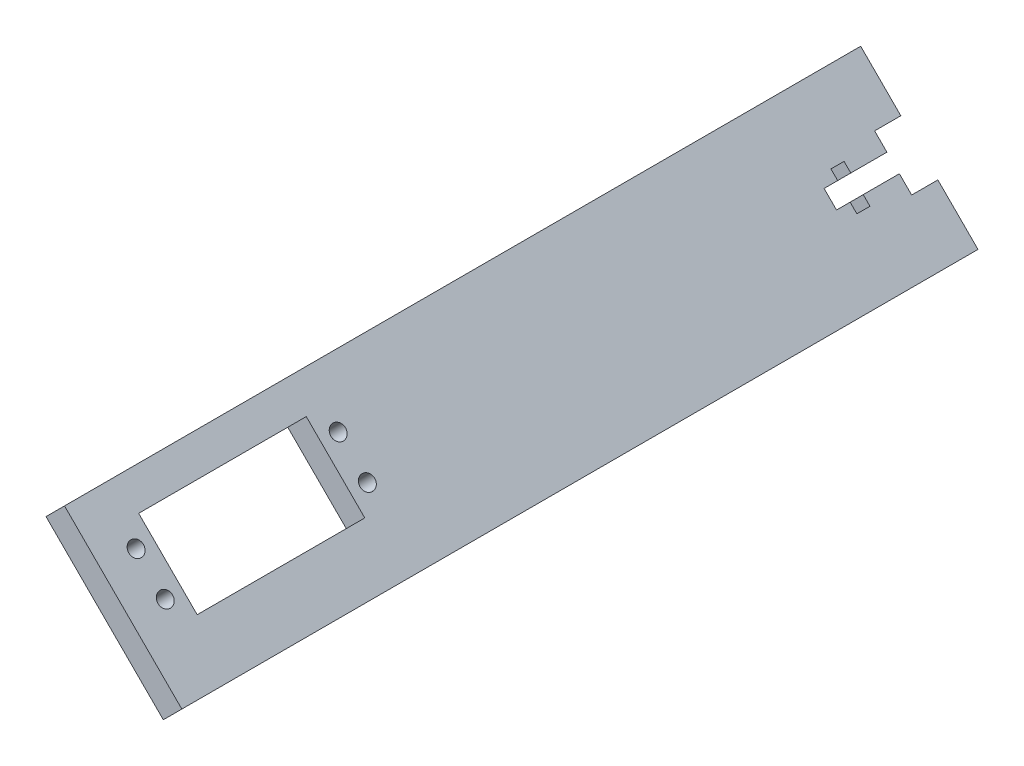
SolidWorks part; units mm, degrees
ref_plane "Front Plane" through (0, 0, 0) normal (0, 0, 1) x (1, 0, 0)
ref_plane "Top Plane" through (0, 0, 0) normal (0, 1, 0) x (1, 0, 0)
ref_plane "Right Plane" through (0, 0, 0) normal (1, 0, 0) x (0, 0, -1)
sketch "Sketch2" plane through (0, 0, 0) normal (0, 0, 1) x (1, 0, 0)
  line L0 (-71.1005, -144.0441) -> (-75.5906, -148.5343)
  line L1 (-71.1005, -144.0441) -> (-42.6562, -172.4884)
  line L2 (-75.5906, -148.5343) -> (-47.1463, -176.9785)
  line L3 (-42.6562, -172.4884) -> (-47.1463, -176.9785)
  line L4 (-75.5906, -148.5343) -> (-65.8586, -158.2663) construction
  line L5 (-61.3685, -153.7761) -> (-71.1005, -144.0441) construction
  line L6 (-47.1463, -176.9785) -> (-42.6562, -172.4884) construction
  line L7 (-71.1005, -144.0441) -> (-75.5906, -148.5343) construction
extrude "Boss-Extrude1" add sketch "Sketch2" along normal blind 186.69
sketch "Sketch3" plane through (-112.0624, -112.0624, 0) normal (-0.7071, -0.7071, 0) x (0, 0, 1)
  line L0 (0, -71.6921) -> (24.1393, -71.6921) construction
  line L1 (0, -51.579) -> (0, -91.8052) construction
  line B0 (0, -69.5585) -> (0, -73.8257)
  line B1 (11.938, -73.8257) -> (11.938, -76.1371)
  line B2 (11.938, -76.1371) -> (8.763, -76.1371)
  line B3 (8.763, -76.1371) -> (8.763, -73.8257)
  line B4 (8.763, -73.8257) -> (0, -73.8257)
  line B5 (11.938, -73.8257) -> (15.24, -73.8257)
  line B6 (15.24, -73.8257) -> (15.24, -69.5585)
  line B7 (11.938, -69.5585) -> (15.24, -69.5585)
  line B8 (8.763, -69.5585) -> (0, -69.5585)
  line B9 (8.763, -67.2471) -> (8.763, -69.5585)
  line B10 (11.938, -67.2471) -> (8.763, -67.2471)
  line B11 (11.938, -69.5585) -> (11.938, -67.2471)
sketch_block_instance "TSlot-1"
sketch_block "TSlot" parameters "D1"=3.302, "D2"=3.175
extrude "Cut-Extrude1" cut sketch "Sketch3" against normal through all
sketch "Sketch4" plane through (0, 0, 0) normal (0, 0, -1) x (-1, 0, 0)
  line L0 (75.5906, -148.5343) -> (65.8586, -158.2663) construction
  line L1 (65.8586, -158.2663) -> (61.3685, -153.7761) construction
  line L2 (61.3685, -153.7761) -> (71.1005, -144.0441) construction
  line L3 (71.1005, -144.0441) -> (75.5906, -148.5343) construction
  line L4 (42.6562, -172.4884) -> (52.3882, -162.7564) construction
  line L5 (52.3882, -162.7564) -> (56.8783, -167.2465) construction
  line L6 (56.8783, -167.2465) -> (47.1463, -176.9785) construction
  line L7 (47.1463, -176.9785) -> (42.6562, -172.4884) construction
  line L8 (75.5906, -148.5343) -> (65.8586, -158.2663)
  line L9 (65.8586, -158.2663) -> (61.3685, -153.7761)
  line L10 (61.3685, -153.7761) -> (71.1005, -144.0441)
  line L11 (71.1005, -144.0441) -> (75.5906, -148.5343)
  line L12 (42.6562, -172.4884) -> (52.3882, -162.7564)
  line L13 (52.3882, -162.7564) -> (56.8783, -167.2465)
  line L14 (56.8783, -167.2465) -> (47.1463, -176.9785)
  line L15 (47.1463, -176.9785) -> (42.6562, -172.4884)
extrude "Boss-Extrude2" add sketch "Sketch4" along normal blind 6.35
sketch "Sketch5" plane through (-107.5723, -107.5723, 0) normal (0.7071, 0.7071, 0) x (0, 0, -1)
  line L1 (-173.99, -59.0392) -> (-133.35, -59.0392)
  line L2 (-173.99, -59.0392) -> (-173.99, -79.1052)
  line L3 (-173.99, -79.1052) -> (-133.35, -79.1052)
  line L4 (-133.35, -59.0392) -> (-133.35, -79.1052)
  line L5 (-186.69, -91.8052) -> (-186.69, -51.579) construction
  line L6 (-165.1552, -59.0392) -> (-139.1365, -59.0392) construction
  line L7 (-139.1365, -79.1052) -> (-164.2745, -79.1052) construction
  line L8 (-165.1552, -59.0392) -> (-139.1365, -59.0392) construction
  line L9 (-139.1365, -79.1052) -> (-164.2745, -79.1052) construction
  dimension "D1" = 40.64
  dimension "D2" = 12.7
extrude "Cut-Extrude2" cut sketch "Sketch5" against normal through all
sketch "Sketch6" plane through (-107.5723, -107.5723, 0) normal (0.7071, 0.7071, 0) x (0, 0, -1)
  arc A4 (-179.4143, -65.3422) -> (-179.4143, -62.8022) centre (-178.17, -64.0722) ccw construction
  arc A5 (-179.4143, -75.3422) -> (-179.4143, -72.8022) centre (-178.17, -74.0722) ccw construction
  arc A6 (-127.9257, -62.8022) -> (-127.9257, -65.3422) centre (-129.17, -64.0722) ccw construction
  arc A7 (-127.9257, -72.8022) -> (-127.9257, -75.3422) centre (-129.17, -74.0722) ccw construction
  circle A8 centre (-178.17, -64.0722) radius 1.778
  circle A9 centre (-178.17, -74.0722) radius 1.778
  circle A10 centre (-129.17, -64.0722) radius 1.778
  circle A11 centre (-129.17, -74.0722) radius 1.778
extrude "Cut-Extrude4" cut sketch "Sketch6" against normal through all
